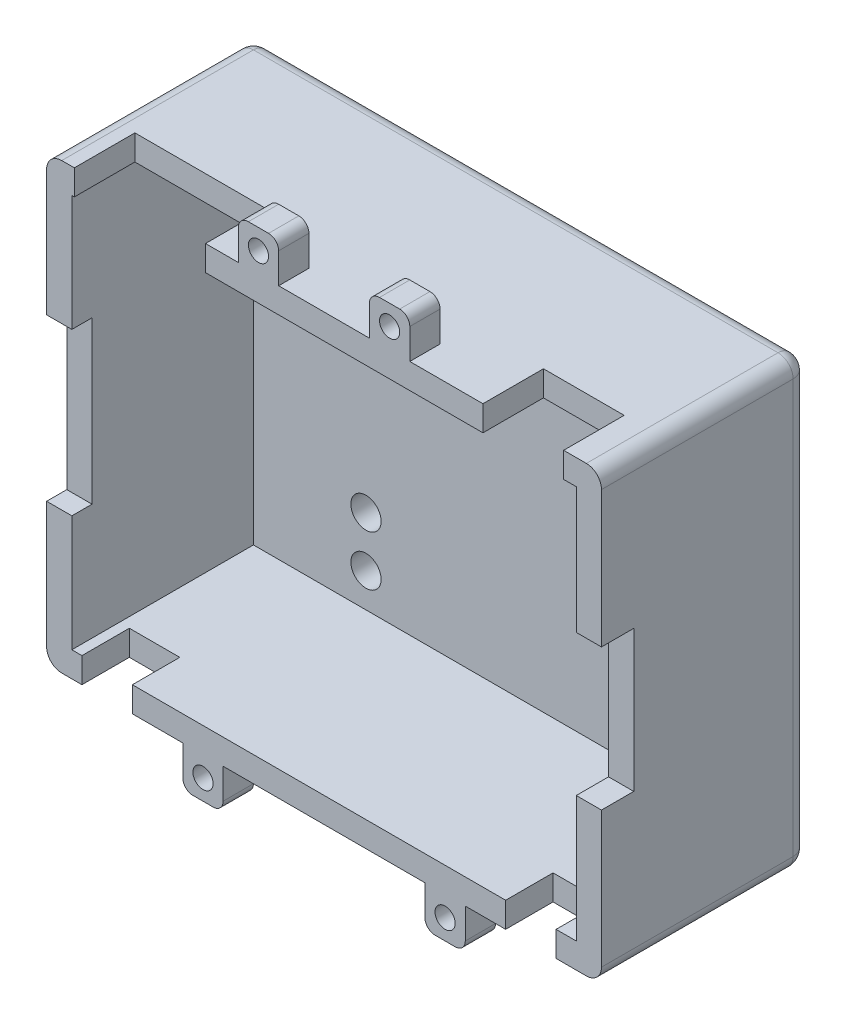
SolidWorks part; units mm, degrees
ref_plane "Front" through (0, 0, 0) normal (0, 0, 1) x (1, 0, 0)
ref_plane "Top" through (0, 0, 0) normal (0, 1, 0) x (1, 0, 0)
ref_plane "Right" through (0, 0, 0) normal (1, 0, 0) x (0, 0, -1)
sketch "草图1" plane through (0, 0, 0) normal (0, 0, 1) x (1, 0, 0)
  line L0 (0, 27.1437) -> (0, -32.4356) construction
  line L1 (-40.784, 0) -> (40.784, 0) construction
  line L3 (-25.5, 19.5) -> (24.5, 19.5)
  line L4 (-25.5, 19.5) -> (-25.5, -19.5)
  line L5 (-25.5, -19.5) -> (24.5, -19.5)
  line L6 (24.5, 19.5) -> (24.5, -19.5)
  dimension "D1" = 24.5
  dimension "D2" = 25.5
  dimension "D3" = 19.5
  dimension "D4" = 19.5
extrude "凸台-拉伸1" add sketch "草图1" against normal blind 2.5
sketch "草图2" plane through (0, 0, -2.5) normal (0, 0, -1) x (-1, 0, 0)
  line L0 (-24.5, 19.5) -> (25.5, 19.5) construction
  line L1 (-27, 22) -> (28, 22)
  line L2 (-27, 22) -> (-27, -22)
  line L3 (-27, -22) -> (28, -22)
  line L4 (28, 22) -> (28, -22)
  line L5 (25.5, -19.5) -> (-24.5, -19.5) construction
  line L6 (25.5, 19.5) -> (25.5, -19.5) construction
  line L7 (-24.5, -19.5) -> (-24.5, 19.5) construction
  dimension "D1" = 2.5
  dimension "D2" = 2.5
  dimension "D3" = 2.5
  dimension "D4" = 2.5
extrude "拉伸-薄壁2" add sketch "草图2" against normal blind 20.5 thin thin type one direction reverse wall 2.5
fillet "圆角1" radius 1.5 4 edges at (-28, 22, 7.75) (-28, -22, 7.75) (27, -22, 7.75) (27, 22, 7.75)
sketch "草图3" plane through (0, -22, 0) normal (0, -1, 0) x (1, 0, 0)
  line L0 (25.5, 18) -> (-26.5, 18) construction
  line L1 (13.5, 15) -> (9.5, 15)
  line L2 (-14.5, 18) -> (-10.5, 18)
  line L3 (-14.5, 18) -> (-14.5, 15)
  line L4 (-14.5, 15) -> (-10.5, 15)
  line L5 (-10.5, 18) -> (-10.5, 15)
  line L6 (-0.5, 16) -> (-0.5, 34.4036) construction
  line L7 (-0.5, 34.4036) -> (-0.5, -10.9095) construction
  line L8 (13.5, 18) -> (9.5, 18)
  line L9 (13.5, 18) -> (13.5, 15)
  line L10 (9.5, 18) -> (9.5, 15)
  dimension "D1" = 4
  dimension "D2" = 10
  dimension "D3" = 3
extrude "凸台-拉伸2" add sketch "草图3" along normal blind 4
fillet "圆角2" radius 1 4 edges at (13.5, -26, 16.5) (9.5, -26, 16.5) (-10.5, -26, 16.5) (-14.5, -26, 16.5)
sketch "草图4" plane through (0, 22, 0) normal (0, 1, 0) x (1, 0, 0)
  line L0 (-26.5, -18) -> (25.5, -18) construction
  line L1 (-0.5, 2.5) -> (-0.5, 14.9374) construction
  line L2 (-0.5, 14.9374) -> (-0.5, -41.0179) construction
  line L3 (-9, -18) -> (-5, -18)
  line L4 (-9, -18) -> (-9, -15)
  line L5 (-9, -15) -> (-5, -15)
  line L6 (-5, -18) -> (-5, -15)
  line L7 (8, -15) -> (4, -15)
  line L8 (4, -18) -> (4, -15)
  line L9 (8, -18) -> (4, -18)
  line L10 (8, -18) -> (8, -15)
  dimension "D1" = 4.5
  dimension "D2" = 4
  dimension "D3" = 3
extrude "凸台-拉伸3" add sketch "草图4" along normal blind 4
fillet "圆角3" radius 1 4 edges at (8, 26, 16.5) (4, 26, 16.5) (-5, 26, 16.5) (-9, 26, 16.5)
sketch "草图5" plane through (0, 0, 18) normal (0, 0, 1) x (1, 0, 0)
  line L1 (24.5, 6.9912) -> (27, 6.9912)
  line L2 (24.5, 6.9912) -> (24.5, -7.0088)
  line L3 (24.5, -7.0088) -> (27, -7.0088)
  line L4 (27, 6.9912) -> (27, -7.0088)
  line L6 (27, 20.5) -> (27, -20.5) construction
  line L7 (24.5, -0.0088) -> (38.0278, -0.0088) construction
  line L9 (24.5, 19.5) -> (24.5, -19.5) construction
  dimension "D1" = 7
  dimension "D2" = 7
extrude "切除-拉伸1" cut sketch "草图5" against normal blind 3.2
sketch "草图6" plane through (0, 0, 18) normal (0, 0, 1) x (1, 0, 0)
  line L3 (-18.7722, 19.5) -> (-18.75, 22) construction
  line L4 (-25, 22) -> (-12.5, 22) construction
  line L5 (-18.75, 22) -> (-18.75, 27.8224) construction
  line L7 (-25.5, 19.5) -> (24.5, 19.5) construction
  line L8 (-25.25, 19.5) -> (-12.25, 19.5)
  line L9 (-25.25, 19.5) -> (-25.25, 22)
  line L10 (-25.25, 22) -> (-12.25, 22)
  line L11 (-12.25, 19.5) -> (-12.25, 22)
  line L12 (-26.5, 22) -> (-9, 22) construction
  dimension "D1" = 6.5
  dimension "D2" = 6.5
extrude "切除-拉伸2" cut sketch "草图6" against normal blind 6
sketch "草图7" plane through (0, 0, 18) normal (0, 0, 1) x (1, 0, 0)
  line L0 (-12.25, 19.5) -> (24.5, 19.5) construction
  line L3 (19.25, 24.2333) -> (19.25, 18.0691) construction
  line L4 (15.25, 19.5) -> (23.25, 19.5)
  line L5 (15.25, 19.5) -> (15.25, 22)
  line L6 (15.25, 22) -> (23.25, 22)
  line L7 (23.25, 19.5) -> (23.25, 22)
  line L8 (8, 22) -> (25.5, 22) construction
  dimension "D1" = 4
  dimension "D2" = 4
extrude "切除-拉伸3" cut sketch "草图7" against normal blind 6
sketch "草图8" plane through (0, 0, 18) normal (0, 0, 1) x (1, 0, 0)
  line L0 (35.85, 0) -> (-12.6658, 0) construction
  line L1 (35.85, -3) -> (35.85, 3) construction
  line L2 (-28, -20.5) -> (-28, 20.5) construction
  line L3 (-28, 8) -> (-25.5, 8)
  line L4 (-28, 8) -> (-28, -8)
  line L5 (-28, -8) -> (-25.5, -8)
  line L6 (-25.5, 8) -> (-25.5, -8)
  line L7 (-25.5, -19.5) -> (-25.5, 19.5) construction
  dimension "D1" = 8
  dimension "D2" = 8
extrude "切除-拉伸4" cut sketch "草图8" against normal blind 2
fillet "圆角4" radius 1.5 8 edges at (-27.5607, 21.5607, -2.5) (-28, 0, -2.5) (-27.5607, -21.5607, -2.5) (-0.5, -22, -2.5) (26.5607, -21.5607, -2.5) (27, 0, -2.5) (26.5607, 21.5607, -2.5) (-0.5, 22, -2.5)
sketch "草图9" plane through (0, 0, 0) normal (0, 0, 1) x (1, 0, 0)
  circle A0 centre (-14.3436, -16.1373) radius 1.5
  circle A1 centre (-14.3436, -11.1546) radius 1.5
  dimension "D1" = 3
extrude "切除-拉伸5" cut sketch "草图9" against normal up to next
sketch "草图10" plane through (0, 0, 0) normal (0, 0, 1) x (1, 0, 0)
  line L1 (16.8654, 11.9541) -> (22.3654, 11.9541)
  line L2 (16.8654, 11.9541) -> (16.8654, -7.6459)
  line L3 (16.8654, -7.6459) -> (22.3654, -7.6459)
  line L4 (22.3654, 11.9541) -> (22.3654, -7.6459)
  dimension "D1" = 5.5
  dimension "D2" = 19.6
extrude "凸台-拉伸4" add sketch "草图10" along normal blind 2
sketch "草图11" plane through (0, 0, 2) normal (0, 0, 1) x (1, 0, 0)
  line L0 (16.8654, 2.1541) -> (22.3654, 2.1541) construction
  line L1 (16.8654, 11.9541) -> (16.8654, -7.6459) construction
  line L2 (22.3654, -7.6459) -> (22.3654, 11.9541) construction
  line L3 (19.6154, 11.9541) -> (19.6154, -7.6459) construction
  line L4 (22.3654, 11.9541) -> (16.8654, 11.9541) construction
  line L5 (16.8654, -7.6459) -> (22.3654, -7.6459) construction
  line L7 (18.0154, 5.3541) -> (21.2154, 5.3541)
  line L8 (18.0154, 5.3541) -> (18.0154, -1.0459)
  line L9 (18.0154, -1.0459) -> (21.2154, -1.0459)
  line L10 (21.2154, 5.3541) -> (21.2154, -1.0459)
  dimension "D1" = 6.4
  dimension "D2" = 3.2
extrude "切除-拉伸6" cut sketch "草图11" against normal up to next
sketch "草图12" plane through (0, 0, 18) normal (0, 0, 1) x (1, 0, 0)
  line L0 (24.5, -19.5) -> (-25.5, -19.5) construction
  line L1 (17.5, -19.5) -> (22.5, -19.5)
  line L2 (17.5, -19.5) -> (17.5, -22)
  line L3 (17.5, -22) -> (22.5, -22)
  line L4 (22.5, -19.5) -> (22.5, -22)
  line L5 (25.5, -22) -> (13.5, -22) construction
  line L6 (17.75, -18.5) -> (17.75, -21.1) construction
  line L7 (22.25, -18.5) -> (22.25, -21.1) construction
  line L8 (-14.5, -22) -> (-26.5, -22) construction
  line L9 (-24.5, -19.5) -> (-19.5, -19.5)
  line L10 (-24.5, -19.5) -> (-24.5, -22)
  line L11 (-24.5, -22) -> (-19.5, -22)
  line L12 (-19.5, -19.5) -> (-19.5, -22)
  line L13 (-24.25, -18.5) -> (-24.25, -21.1) construction
  line L14 (-19.75, -18.5) -> (-19.75, -21.1) construction
  dimension "D1" = 0.25
  dimension "D2" = 0.25
  dimension "D3" = 0.25
  dimension "D4" = 0.25
extrude "切除-拉伸7" cut sketch "草图12" against normal blind 4.7
sketch "草图14" plane through (0, 0, 0) normal (0, 0, 1) x (1, 0, 0)
  line L0 (19.6154, -1.0459) -> (19.6154, -23.1066) construction
  line L1 (18.0154, -1.0459) -> (21.2154, -1.0459) construction
  circle A0 centre (19.6154, -10.757) radius 1.5
  dimension "D1" = 3
extrude "切除-拉伸8" cut sketch "草图14" against normal up to next
sketch "草图16" plane through (0, 0, 15) normal (0, 0, -1) x (-1, 0, 0)
  line L0 (-8, 25) -> (-8, 22) construction
  line L2 (-7, 26) -> (-5, 26) construction
  line L3 (5, 25) -> (5, 22) construction
  line L4 (6, 26) -> (8, 26) construction
  line L5 (-13.5, -25) -> (-13.5, -22) construction
  line L6 (26.5, -22) -> (-25.5, -22) construction
  line L7 (10.5, -25) -> (10.5, -22) construction
  circle A0 centre (-6, 24) radius 1
  circle A1 centre (7, 24) radius 1
  circle A2 centre (-11.5, -24) radius 1
  circle A3 centre (12.5, -24) radius 1
  dimension "D1" = 2
  dimension "D4" = 2
  dimension "D7" = 2
  dimension "D10" = 2
  dimension "D2" = 2
  dimension "D3" = 2
  dimension "D5" = 2
  dimension "D6" = 2
  dimension "D8" = 2
  dimension "D9" = 2
  dimension "D11" = 2
  dimension "D12" = 2
extrude "切除-拉伸9" cut sketch "草图16" against normal up to next
sketch "草图17" plane through (0, 0, 2) normal (0, 0, 1) x (1, 0, 0)
  line L0 (16.8654, 2.1541) -> (29.2529, 2.1541) construction
  line L1 (16.8654, 11.9541) -> (16.8654, -7.6459) construction
  line L2 (19.6154, 11.9541) -> (19.6154, -13.8346) construction
  line L3 (22.3654, 11.9541) -> (16.8654, 11.9541) construction
  circle A0 centre (19.6154, 9.6541) radius 1
  circle A1 centre (19.6154, -5.3459) radius 1
  dimension "D1" = 2
  dimension "D2" = 7.5
extrude "切除-拉伸10" cut sketch "草图17" against normal blind 4
thread "螺纹线1" pitch 0.4 method cut profile "螺纹线轮廓1" start angle 0, offset 0, length 4, pitch 0.4, diameter 2
ref_plane "基准面1" through (18.6154, 9.6541, 2) normal (0, -1, 0) x (-1, 0, 0)
sketch "螺纹线轮廓1" plane through (18.6154, 9.6541, 2) normal (0, -1, 0) x (-1, 0, 0)
  line L0 (0, 0) -> (0, 0.4) construction
  line L1 (0, 0) -> (0.2165, 0.125)
  line L2 (0.2165, 0.125) -> (0.2165, 0.175)
  line L3 (0.2165, 0.175) -> (0, 0.3)
  line L4 (0.2165, 0.15) -> (0, 0.15) construction
  line L11 (0, 0) -> (0, 0.3)
  point P2 (0, 0)
  dimension "Pitch" = 0.4
  dimension "Profile_Angle" = 60
  dimension "Profile_Land" = 0.05
  dimension "Profile_Height" = 0.2165
thread "螺纹线2" pitch 0.4 method cut profile "螺纹线轮廓2" start angle 0, offset 0, length 4, pitch 0.4, diameter 2
ref_plane "基准面2" through (18.6154, -5.3459, 2) normal (0, -1, 0) x (-1, 0, 0)
sketch "螺纹线轮廓2" plane through (18.6154, -5.3459, 2) normal (0, -1, 0) x (-1, 0, 0)
  line L0 (0, 0) -> (0, 0.4) construction
  line L1 (0, 0) -> (0.2165, 0.125)
  line L2 (0.2165, 0.125) -> (0.2165, 0.175)
  line L3 (0.2165, 0.175) -> (0, 0.3)
  line L4 (0.2165, 0.15) -> (0, 0.15) construction
  line L11 (0, 0) -> (0, 0.3)
  point P2 (0, 0)
  dimension "Pitch" = 0.4
  dimension "Profile_Angle" = 60
  dimension "Profile_Land" = 0.05
  dimension "Profile_Height" = 0.2165
equation "\"2.5.00mm\"=10"
